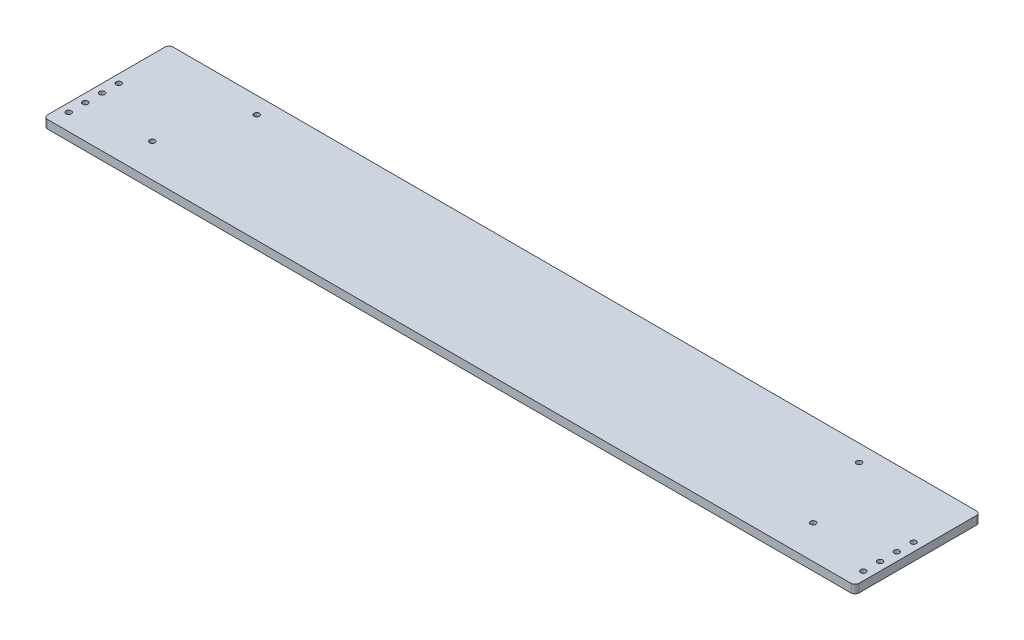
SolidWorks part; units mm, degrees
material "PC High Viscosity"
ref_plane "Front Plane" through (0, 0, 0) normal (0, 0, 1) x (1, 0, 0)
ref_plane "Top Plane" through (0, 0, 0) normal (0, 1, 0) x (1, 0, 0)
ref_plane "Right Plane" through (0, 0, 0) normal (1, 0, 0) x (0, 0, -1)
sketch "Sketch1" plane through (0, 0, 0) normal (0, 1, 0) x (1, 0, 0)
  line L0 (-301.625, 3.175) -> (-301.625, -34.925) construction
  line L1 (-307.975, -47.625) -> (307.975, -47.625)
  line L2 (-307.975, -47.625) -> (-307.975, 47.625)
  line L3 (-307.975, 47.625) -> (307.975, 47.625)
  line L4 (307.975, -47.625) -> (307.975, 47.625)
  line L5 (-307.975, -47.625) -> (307.975, 47.625) construction
  line L6 (-307.975, 47.625) -> (307.975, -47.625) construction
  line L7 (0, 47.625) -> (0, -47.625) construction
  circle A2 centre (-301.625, 3.175) radius 2.0193
  circle A3 centre (-301.625, -9.525) radius 2.0193
  circle A4 centre (-301.625, -22.225) radius 2.0193
  circle A5 centre (-301.625, -34.925) radius 2.0193
  circle A6 centre (301.625, -34.925) radius 2.0193
  circle A7 centre (301.625, -22.225) radius 2.0193
  circle A8 centre (301.625, -9.525) radius 2.0193
  circle A9 centre (301.625, 3.175) radius 2.0193
  point P0 (0, 0)
  dimension "D3" = 6.35
  dimension "D4" = 4.0386
  dimension "D5" = 4
  dimension "D6" = 44.45
  dimension "D7" = 12.7
  dimension "D1" = 95.25
  dimension "D2" = 615.95
extrude "Boss-Extrude1" add sketch "Sketch1" along normal blind 6.35
fillet "Fillet1" radius 3.175 4 edges at (307.975, 3.175, 47.625) (-307.975, 3.175, -47.625) (307.975, 3.175, -47.625) (-307.975, 3.175, 47.625)
sketch "Sketch2" plane through (0, 6.35, 0) normal (0, 1, 0) x (1, 0, 0)
  line L0 (304.8, 47.625) -> (-304.8, 47.625) construction
  line L1 (-307.975, 44.45) -> (-307.975, -44.45) construction
  line L2 (-304.8, -47.625) -> (304.8, -47.625) construction
  line L3 (0, 47.625) -> (0, -47.625) construction
  circle A0 centre (-228.6, 34.925) radius 2.0193
  circle A1 centre (-250.825, -22.225) radius 2.0193
  circle A2 centre (-250.825, -22.225) radius 25.4 construction
  circle A3 centre (-228.6, 34.925) radius 25.4 construction
  circle A4 centre (250.825, -22.225) radius 25.4 construction
  circle A5 centre (250.825, -22.225) radius 2.0193
  circle A6 centre (228.6, 34.925) radius 25.4 construction
  circle A7 centre (228.6, 34.925) radius 2.0193
  dimension "D1" = 4.0386
  dimension "D2" = 50.8
  dimension "D3" = 50.8
  dimension "D4" = 12.7
  dimension "D6" = 25.4
  dimension "D7" = 79.375
  dimension "D5" = 57.15
extrude "Cut-Extrude1" cut sketch "Sketch2" against normal through all
